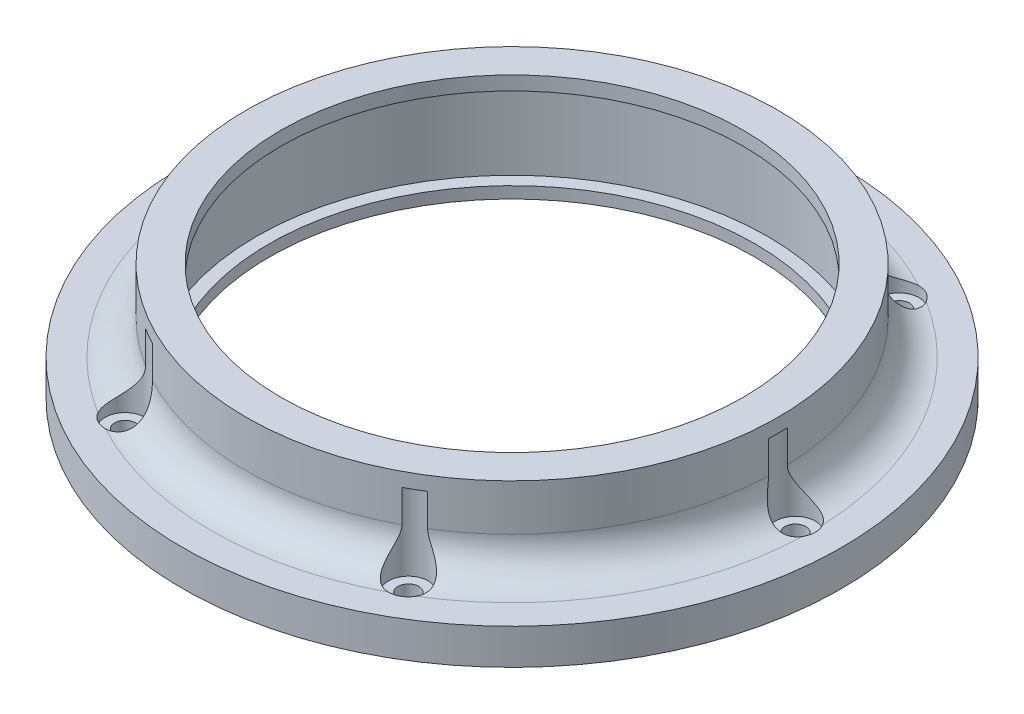
SolidWorks part; units mm, degrees
ref_plane "Front Plane" through (0, 0, 0) normal (0, 0, 1) x (1, 0, 0)
ref_plane "Top Plane" through (0, 0, 0) normal (0, 1, 0) x (1, 0, 0)
ref_plane "Right Plane" through (0, 0, 0) normal (1, 0, 0) x (0, 0, -1)
sketch "Sketch1" plane through (0, 0, 0) normal (0, 1, 0) x (1, 0, 0)
  circle A0 centre (0, 0) radius 61.25 construction
  circle A1 centre (0, 0) radius 55.25
  circle A2 centre (0, 0) radius 57.5
  dimension "D1" = 122.5
  dimension "D2" = 110.5
  dimension "D3" = 115
extrude "Boss-Extrude1" add sketch "Sketch1" along normal blind 22
sketch "Sketch2" plane through (0, 0, 0) normal (0, -1, 0) x (1, 0, 0)
  circle A0 centre (0, 0) radius 61.25 construction
  circle A1 centre (0, 0) radius 71.25
  circle A2 centre (0, 0) radius 57.5 construction
  circle A3 centre (0, 0) radius 57.5
  dimension "D1" = 122.5
  dimension "D2" = 10
extrude "Boss-Extrude2" add sketch "Sketch2" against normal blind 7.5
hole_wizard "CBORE for M4 SBHCS1" positions "Sketch6" profile "Sketch5" counterbore size "M4" standard "ANSI Metric" end condition through all
sketch "Sketch6" plane through (0, 7.5, 0) normal (0, 1, 0) x (1, 0, 0)
  circle A0 centre (0, 0) radius 61.25 construction
  point P0 (-61.25, 0)
  dimension "D1" = 122.5
sketch "Sketch5" plane through (-61.25, 7.5, 0) normal (1, 0, 0) x (0, 0, 1)
  line L0 (0, 0) -> (0, 7.5)
  line L1 (0, 7.5) -> (2.25, 7.5)
  line L3 (2.25, 7.5) -> (2.25, 2.2)
  line L4 (2.25, 2.2) -> (4.3, 2.2)
  line L5 (4.3, 2.2) -> (4.3, 0)
  line L7 (4.3, 0) -> (0, 0)
  line L11 (0, -6.35) -> (0, 107.95) construction
  dimension "Thru Hole Dia." = 4.5
  dimension "Thru Hole Depth" = 7.5
  dimension "C'Bore Dia." = 8.6
  dimension "C'Bore Depth" = 2.2
fillet "Fillet2" radius 7.5 1 edges at (57.5, 7.5, 0)
sketch "Sketch7" plane through (0, 7.5, 0) normal (0, 1, 0) x (1, 0, 0)
  circle A1 centre (-61.25, 0) radius 4.3
  circle A2 centre (-61.25, 0) radius 4.3
  dimension "D1" = 0
extrude "Cut-Extrude1" cut sketch "Sketch7" along normal through all
pattern_circular "CirPattern1" count 6 over 360 about axis through (0, 7.5, 0) along (0, -1, 0) of "Cut-Extrude1", "CBORE for M4 SBHCS1"
sketch "Sketch8" plane through (0, 0, 0) normal (0, 1, 0) x (1, 0, 0)
  circle A0 centre (0, 0) radius 52.5
  arc A12 (-57.4639, -2.0384) -> (-30.4972, -48.746) centre (0, 0) ccw
  arc A13 (-26.9666, -50.7844) -> (-30.4972, -48.746) centre (-30.625, -53.0441) ccw
  arc A14 (-26.9666, -50.7844) -> (26.9666, -50.7844) centre (0, 0) ccw
  arc A15 (30.4972, -48.746) -> (26.9666, -50.7844) centre (30.625, -53.0441) ccw
  arc A16 (30.4972, -48.746) -> (57.4639, -2.0384) centre (0, 0) ccw
  arc A17 (57.4639, 2.0384) -> (57.4639, -2.0384) centre (61.25, 0) ccw
  arc A18 (57.4639, 2.0384) -> (30.4972, 48.746) centre (0, 0) ccw
  arc A19 (26.9666, 50.7844) -> (30.4972, 48.746) centre (30.625, 53.0441) ccw
  arc A20 (26.9666, 50.7844) -> (-26.9666, 50.7844) centre (0, 0) ccw
  arc A21 (-30.4972, 48.746) -> (-26.9666, 50.7844) centre (-30.625, 53.0441) ccw
  arc A22 (-30.4972, 48.746) -> (-57.4639, 2.0384) centre (0, 0) ccw
  arc A23 (-57.4639, -2.0384) -> (-57.4639, 2.0384) centre (-61.25, 0) ccw
  arc A24 (-57.4639, -2.0384) -> (-30.4972, -48.746) centre (0, 0) ccw
  arc A25 (-26.9666, -50.7844) -> (-30.4972, -48.746) centre (-30.625, -53.0441) ccw
  arc A26 (-26.9666, -50.7844) -> (26.9666, -50.7844) centre (0, 0) ccw
  arc A27 (30.4972, -48.746) -> (26.9666, -50.7844) centre (30.625, -53.0441) ccw
  arc A28 (30.4972, -48.746) -> (57.4639, -2.0384) centre (0, 0) ccw
  arc A29 (57.4639, 2.0384) -> (57.4639, -2.0384) centre (61.25, 0) ccw
  arc A30 (57.4639, 2.0384) -> (30.4972, 48.746) centre (0, 0) ccw
  arc A31 (26.9666, 50.7844) -> (30.4972, 48.746) centre (30.625, 53.0441) ccw
  arc A32 (26.9666, 50.7844) -> (-26.9666, 50.7844) centre (0, 0) ccw
  arc A33 (-30.4972, 48.746) -> (-26.9666, 50.7844) centre (-30.625, 53.0441) ccw
  arc A34 (-30.4972, 48.746) -> (-57.4639, 2.0384) centre (0, 0) ccw
  arc A35 (-57.4639, -2.0384) -> (-57.4639, 2.0384) centre (-61.25, 0) ccw
  dimension "D2" = 5
  dimension "D1" = 0
extrude "Boss-Extrude3" add sketch "Sketch8" along normal blind 2.5
sketch "Sketch10" plane through (0, 0, 0) normal (0, -1, 0) x (1, 0, 0)
  circle A0 centre (0, 0) radius 55.25 construction
  circle A1 centre (0, 0) radius 71.25
  circle A2 centre (0, 0) radius 71.25
  circle A3 centre (61.25, 0) radius 2.25 construction
  circle A4 centre (30.625, 53.0441) radius 2.25 construction
  circle A5 centre (-30.625, 53.0441) radius 2.25 construction
  circle A6 centre (-61.25, 0) radius 2.25 construction
  circle A7 centre (-30.625, -53.0441) radius 2.25 construction
  circle A8 centre (30.625, -53.0441) radius 2.25 construction
  circle A9 centre (0, 0) radius 55.25
  circle A10 centre (61.25, 0) radius 2.25
  circle A11 centre (30.625, 53.0441) radius 2.25
  circle A12 centre (-30.625, 53.0441) radius 2.25
  circle A13 centre (-61.25, 0) radius 2.25
  circle A14 centre (-30.625, -53.0441) radius 2.25
  circle A15 centre (30.625, -53.0441) radius 2.25
  dimension "D1" = 0
extrude "Boss-Extrude4" add sketch "Sketch10" along normal blind 0.2
sketch "Sketch11" plane through (0, 22, 0) normal (0, 1, 0) x (1, 0, 0)
  circle A2 centre (0, 0) radius 57.5
  circle A3 centre (0, 0) radius 50
  dimension "D1" = 115
  dimension "D2" = 100
extrude "Boss-Extrude5" add sketch "Sketch11" along normal blind 3
